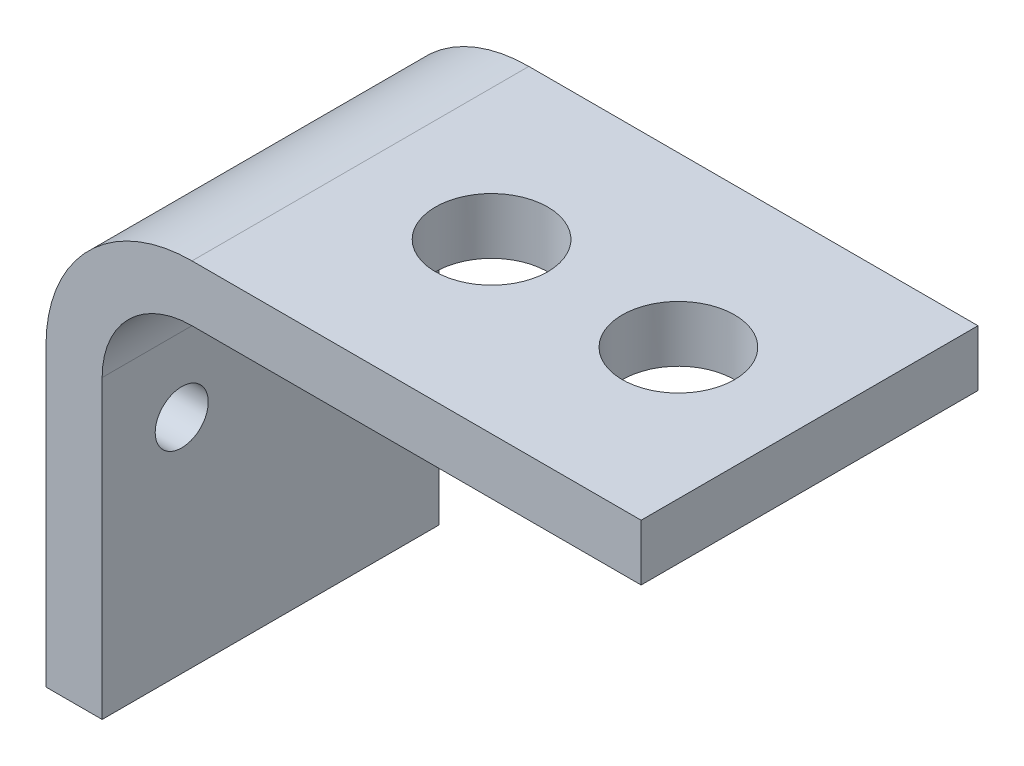
SolidWorks part; units mm, degrees
material "6061 Alloy"
ref_plane "Front Plane" through (0, 0, 0) normal (0, 0, 1) x (1, 0, 0)
ref_plane "Top Plane" through (0, 0, 0) normal (0, 1, 0) x (1, 0, 0)
ref_plane "Right Plane" through (0, 0, 0) normal (1, 0, 0) x (0, 0, -1)
sketch "Sketch1" plane through (0, 0, 0) normal (0, 0, 1) x (1, 0, 0)
  line L0 (0, 0) -> (0, 8.3725)
  line L1 (2.54, 10.9125) -> (15.24, 10.9125)
  line L2 (-1.5875, 0) -> (-1.5875, 8.3725)
  line L3 (2.54, 12.5) -> (15.24, 12.5)
  line L4 (-1.5875, 0) -> (0, 0)
  line L5 (15.24, 10.9125) -> (15.24, 12.5)
  arc A0 (0, 8.3725) -> (2.54, 10.9125) centre (2.54, 8.3725) cw
  arc A1 (-1.5875, 8.3725) -> (2.54, 12.5) centre (2.54, 8.3725) cw
  dimension "D1" = 2.54
  dimension "D2" = 12.7
  dimension "D3" = 12.5
  dimension "D4" = 1.5875
extrude "Boss-Extrude1" add sketch "Sketch1" along normal blind 9.525
sketch "Sketch2" plane through (0, 0, 0) normal (1, 0, 0) x (0, 0, -1)
  line L4 (0, 0) -> (0, 8.3725)
  line L5 (0, 8.3725) -> (-9.525, 8.3725)
  line L6 (-9.525, 8.3725) -> (-9.525, 0)
  line L7 (-9.525, 0) -> (0, 0)
  line L8 (0, 0) -> (0, 8.3725)
  line L9 (0, 8.3725) -> (-9.525, 8.3725)
  line L10 (-9.525, 8.3725) -> (-9.525, 0)
  line L11 (-9.525, 0) -> (0, 0)
  circle A2 centre (-7.275, 6.277) radius 2.0955
  circle A3 centre (-7.275, 6.277) radius 0.75
  dimension "D2" = 1.5
  dimension "D3" = 2.25
  dimension "D1" = 0
extrude "Cut-Extrude1" cut sketch "Sketch2" against normal up to next from surface contours A3 region at (0, 6.277, 7.275) starting at face at (0, 4.1863, 4.7625)
sketch "Sketch3" plane through (0, 10.9125, 0) normal (0, -1, 0) x (1, 0, 0)
  line L0 (15.24, 4.7625) -> (2.54, 4.7625) construction
  line L1 (15.24, 9.525) -> (15.24, 0) construction
  line L2 (2.54, 9.525) -> (2.54, 0) construction
  circle A0 centre (6.2484, 4.7625) radius 1.5875
  circle A1 centre (11.5316, 4.7625) radius 1.5875
  dimension "D1" = 3.7084
  dimension "D3" = 5.2832
  dimension "D2" = 3.7084
extrude "Cut-Extrude2" cut sketch "Sketch3" against normal blind 2.54 contours L0 A0 | L0 A0 | L0 A1 | L0 A1 region at (11.5316, 10.9125, 4.0887) region at (11.5316, 10.9125, 5.4363) region at (6.2484, 10.9125, 4.0887) region at (6.2484, 10.9125, 5.4363)
